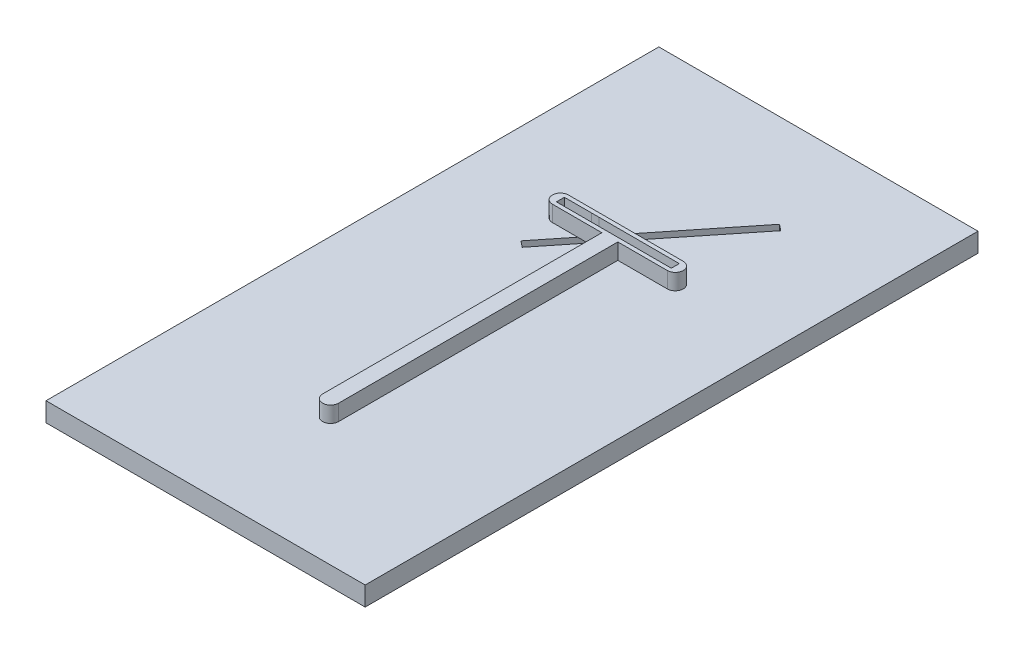
SolidWorks part; units mm, degrees
ref_plane "Front Plane" through (0, 0, 0) normal (0, 0, 1) x (1, 0, 0)
ref_plane "Top Plane" through (0, 0, 0) normal (0, 1, 0) x (1, 0, 0)
ref_plane "Right Plane" through (0, 0, 0) normal (1, 0, 0) x (0, 0, -1)
sketch "Sketch1" plane through (0, 0, 0) normal (0, 1, 0) x (1, 0, 0)
  line L0 (0, -225) -> (0, -135)
  line L1 (-60, -75) -> (60, -75)
  line L2 (-60, -75) -> (-60, 75)
  line L3 (-60, 75) -> (60, 75)
  line L4 (60, -75) -> (60, 75)
  line L5 (-60, -75) -> (60, 75) construction
  line L6 (-60, 75) -> (60, -75) construction
  line L7 (-60, -255) -> (60, -255)
  line L8 (-60, -255) -> (-60, -105)
  line L9 (-60, -105) -> (60, -105)
  line L10 (60, -255) -> (60, -105)
  line L11 (-60, -255) -> (60, -105) construction
  line L12 (-60, -105) -> (60, -255) construction
  line L13 (-36, -45) -> (36, 45)
  line L14 (-36, -20.6843) -> (36, -20.6843)
  line L15 (0, 46.6079) -> (0, -63.8312) construction
  line L16 (0, -20.6843) -> (0, -200.6843)
  line L17 (36, 45) -> (36, -45) construction
  line L18 (-36, -45) -> (36, -45) construction
  line L19 (-34.0478, -46.5617) -> (37.9522, 43.4383)
  line L20 (-37.9522, -43.4383) -> (34.0478, 46.5617)
  line L21 (-34.0478, -46.5617) -> (-37.9522, -43.4383)
  line L22 (37.9522, 43.4383) -> (34.0478, 46.5617)
  line L23 (-32.0957, -48.1235) -> (39.9043, 41.8765)
  line L24 (-39.9043, -41.8765) -> (32.0957, 48.1235)
  line L25 (-36, -25.6843) -> (36, -25.6843)
  line L26 (-36, -15.6843) -> (36, -15.6843)
  line L27 (-36, -23.1843) -> (36, -23.1843)
  line L28 (-36, -18.1843) -> (36, -18.1843)
  line L29 (-36, -23.1843) -> (-36, -18.1843)
  line L30 (36, -23.1843) -> (36, -18.1843)
  line L31 (-5, -20.6843) -> (-5, -200.6843)
  line L32 (5, -20.6843) -> (5, -200.6843)
  line L33 (-19.6962, -20.6448) -> (-17.2772, -17.6211)
  line L34 (-10, -193.7719) -> (10, -193.7719)
  line L35 (-10, -193.7719) -> (-10, -125)
  line L36 (-10, -125) -> (10, -125)
  line L37 (10, -193.7719) -> (10, -125)
  line L38 (-10, -193.7719) -> (10, -125) construction
  line L39 (-10, -125) -> (10, -193.7719) construction
  line L40 (-19.6962, -20.6448) -> (-15.8177, -23.7476)
  line L41 (-17.2772, -17.6211) -> (-13.3987, -20.7239)
  line L42 (-15.8177, -23.7476) -> (-13.3987, -20.7239)
  line L43 (-19.6962, -20.6448) -> (-13.3987, -20.7239) construction
  line L44 (-17.2772, -17.6211) -> (-15.8177, -23.7476) construction
  line L45 (-18.8823, -23.1975) -> (-14.2127, -23.1975)
  line L46 (-18.8823, -23.1975) -> (-18.8823, -18.1712)
  line L47 (-14.2127, -23.1975) -> (-14.2127, -18.1712)
  line L48 (-18.8823, -18.1712) -> (-14.2127, -18.1712)
  line L49 (-18.8823, -23.1975) -> (-14.2127, -18.1712) construction
  line L50 (-14.2127, -23.1975) -> (-18.8823, -18.1712) construction
  line L51 (0, 75) -> (0, 105) construction
  line L52 (-100, 105) -> (100, 105)
  line L53 (-100, 105) -> (-100, -279.0143)
  line L54 (-100, -279.0143) -> (100, -279.0143)
  line L55 (100, 105) -> (100, -279.0143)
  arc A0 (-32.0957, -48.1235) -> (-39.9043, -41.8765) centre (-36, -45) cw
  arc A1 (39.9043, 41.8765) -> (32.0957, 48.1235) centre (36, 45) ccw
  arc A2 (-36, -25.6843) -> (-36, -15.6843) centre (-36, -20.6843) cw
  arc A3 (36, -25.6843) -> (36, -15.6843) centre (36, -20.6843) ccw
  arc A4 (-5, -20.6843) -> (5, -20.6843) centre (0, -20.6843) cw
  arc A5 (-5, -200.6843) -> (5, -200.6843) centre (0, -200.6843) ccw
  point P0 (0, 0)
  point P6 (0, -180)
  point P11 (-16.5475, -20.6843)
  point P14 (0, -180)
  point P17 (0, 0)
  point P20 (0, -200.6843)
  point P46 (0, -159.386)
  point P52 (-16.5475, -20.6843)
  point P53 (-16.5475, -20.6843)
  dimension "D1" = 150
  dimension "D2" = 120
  dimension "D3" = 30
  dimension "D4" = 150
  dimension "D5" = 30
  dimension "D6" = 90
  dimension "D7" = 180
  dimension "D8" = 2.5
  dimension "D18" = 30
  dimension "D19" = 200
  dimension "D20" = 20
  dimension "D21" = 68.7719
  dimension "D24" = 20
  dimension "D9" = 2.5
  dimension "D10" = 5
  dimension "D11" = 5
  dimension "D12" = 5
  dimension "D13" = 5
  dimension "D14" = 2.5
  dimension "D15" = 2.5
  dimension "D16" = 5
  dimension "D17" = 5
extrude "Boss-Extrude2" add sketch "Sketch1" against normal blind 12 contours A3 L25 L32 L1 L4 L3 L2 L31 L23 A0 L24 A2 L26 A1 | A0 L23 L25 L19 L21 L20 L24 | A2 L25 L24 L27 L29 L28 L26 | L32 L25 L16 L1 | L25 L31 L1 L16 | L32 L27 L16 L25 | L32 L14 L16 L27 | A4 L14 L28 | A4 L28 | L14 L31 L27 L16 | L27 L31 L25 L16 | L31 L27 L23 L25 | L31 L14 L23 L27 | L14 A4 L28 L23 | L28 A4 L26 L23 | L26 A4 L28 L30 L27 L32 L25 A3 | L14 L32 L27 L30 | L28 A4 L14 L30 | A5 L31 L34 L35 L36 L9 L8 L7 L10 L32 L37 | L34 L37 L36 L32 | L36 L35 L34 L31 | L36 L16 L34 L32 | L0 A5 L32 L34 | L31 A5 L0 L34 | L36 L31 L34 L16 | L16 L36 L32 L9 | L31 L36 L16 L9 | L32 L1 L16 L9 | L1 L31 L9 L16 | L47 L27 L23 L14 L19 | L28 L19 L14 L23 | L19 L28 L23 L26 | L27 L47 L19 | L29 L27 L24 L14 | L29 L14 L24 L28 | L27 L24 L25 L20 | L24 L27 L20 L14 | L23 A1 L24 L26 L20 L22 L19 | L47 L45 L19 L25 L23 L27 | L46 L20 L28 | L46 L48 L20 L26 L24 L28 | L20 L46 L28 L24 L14 | L55 L52 L53 L54 L1 L32 L9 L10 L7 L8 L31 L2 L3 L4 region at (-2.3631, 0, 199.2491) region at (4.8938, 0, 205.5782) region at (2.3631, 0, 199.2491) region at (-2.5, 0, 159.386) region at (2.5, 0, 159.386) region at (-7.5, 0, 159.386) region at (7.5, 0, 159.386) region at (-2.5, 0, 115) region at (2.5, 0, 115) region at (-2.5, 0, 90) region at (2.5, 0, 90) region at (-2.5, 0, 50.3422) region at (-32.5, 0, 73.0791) region at (2.5, 0, 50.3422) region at (-2.5, 0, 24.4343) region at (-9.0926, 0, 24.4855) region at (5.422, 0, 24.4343) region at (2.5, 0, 24.4343) region at (-14.7451, 0, 24.4367) region at (-23.4029, 0, 36.6776) region at (-2.5, 0, 21.9343) region at (-8.0993, 0, 22.0022) region at (20.5, 0, 21.9343) region at (2.5, 0, 21.9343) region at (-12.5395, 0, 21.8476) region at (0, 0, 19.4631) region at (-6.9974, 0, 19.4984) region at (20.3909, 0, 19.4299) region at (-10.7451, 0, 19.4343) region at (-14.5904, 0, 22.7122) region at (0, 0, 17.1592) region at (-5.0275, 0, 16.8671) region at (-31.4753, 0, 25.4422) region at (-24.3498, 0, 24.4343) region at (-8.7451, 0, 16.9343) region at (-7.7451, 0, 14.795) region at (-29.9615, 0, 21.8998) region at (-22.3498, 0, 21.9343) region at (-20.5555, 0, 19.521) region at (-28.9634, 0, 19.4047) region at (-18.3499, 0, 16.932) region at (-18.5045, 0, 18.6565) region at (0, 0, -100.6703)
extrude "Boss-Extrude4" add sketch "Sketch1<5>" along normal blind 10 from offset 2 contours A2 L25 L24 L27 L29 L28 L26 | L46 L48 L20 L26 L24 L28 | L20 L48 L33 L41 L13 L26 | L13 L48 L47 L28 L19 L26 | L19 L28 L23 L26 | L33 L48 L41 | L28 A4 L26 L23 | A4 L28 | L26 A4 L28 L30 L27 L32 L25 A3 | L32 L27 L16 L25 | L32 L25 L16 L1 | L25 L31 L1 L16 | L27 L31 L25 L16 | L31 L27 L23 L25 | L47 L45 L19 L25 L23 L27 | L27 L24 L25 L20 | L45 L46 L27 L20 L25 L13 | L45 L13 L25 L19 L42 L40 | L45 L40 L42 | L32 L1 L16 L9 | L1 L31 L9 L16 | L16 L36 L32 L9 | L31 L36 L16 L9 | L36 L16 L34 L32 | L36 L31 L34 L16 | L0 A5 L32 L34 | L31 A5 L0 L34 region at (-2.3631, 0, 199.2491) region at (2.3631, 0, 199.2491) region at (-2.5, 0, 159.386) region at (2.5, 0, 159.386) region at (-2.5, 0, 115) region at (2.5, 0, 115) region at (-2.5, 0, 90) region at (2.5, 0, 90) region at (-2.5, 0, 50.3422) region at (2.5, 0, 50.3422) region at (-2.5, 0, 24.4343) region at (-9.0926, 0, 24.4855) region at (5.422, 0, 24.4343) region at (2.5, 0, 24.4343) region at (-14.7451, 0, 24.4367) region at (-18.0351, 0, 24.4839) region at (-21.1496, 0, 24.435) region at (0, 0, 17.1592) region at (-5.0275, 0, 16.8671) region at (-31.4753, 0, 25.4422) region at (-24.3498, 0, 24.4343) region at (-8.7451, 0, 16.9343) region at (-15.9002, 0, 23.3809) region at (-11.9454, 0, 16.9337) region at (-15.0598, 0, 16.8848) region at (-18.3499, 0, 16.932) region at (-17.1947, 0, 17.9878)
sketch "Sketch1<5>" plane through (0, 0, 0) normal (0, 1, 0) x (1, 0, 0) same geometry as "Sketch1"
